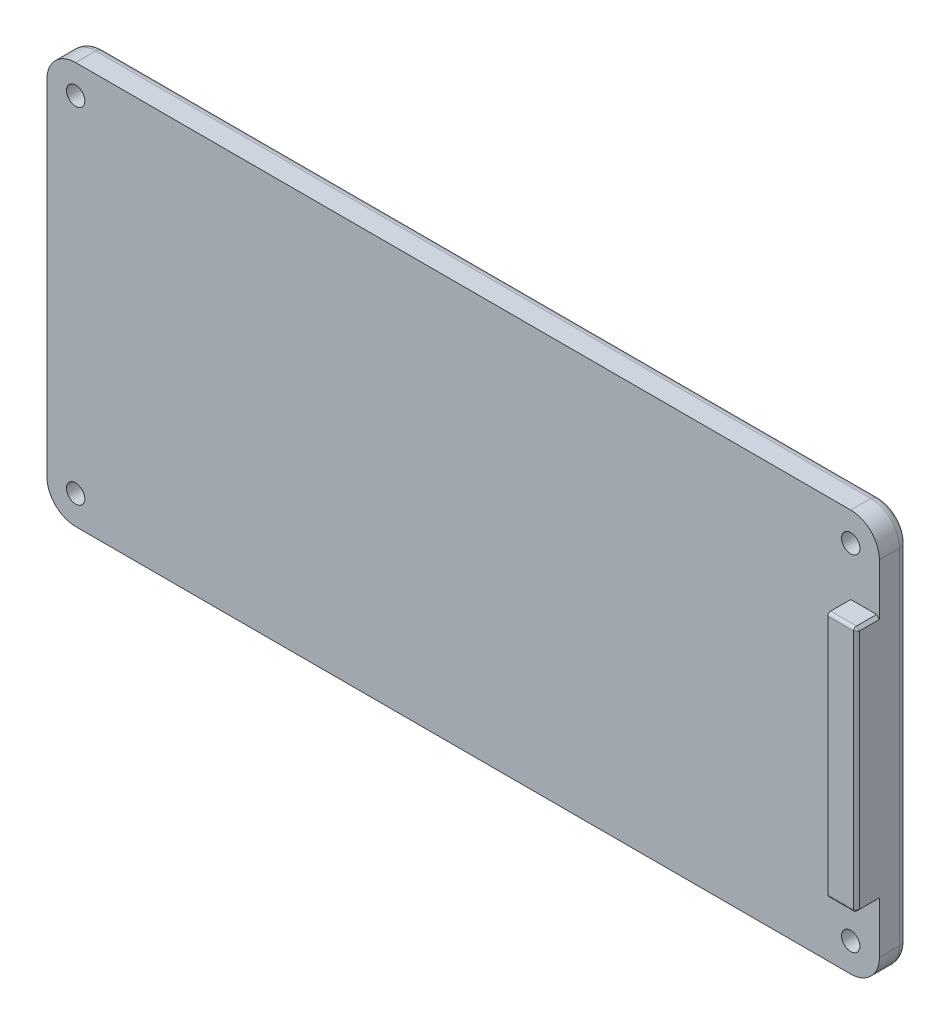
SolidWorks part; units mm, degrees
ref_plane "Ebene vorne" through (0, 0, 0) normal (0, 0, 1) x (1, 0, 0)
ref_plane "Ebene oben" through (0, 0, 0) normal (0, 1, 0) x (1, 0, 0)
ref_plane "Ebene rechts" through (0, 0, 0) normal (1, 0, 0) x (0, 0, -1)
sketch "Skizze1" plane through (0, 0, 0) normal (0, 0, 1) x (1, 0, 0)
  line L1 (-72.5, -35) -> (72.5, -35)
  line L2 (-72.5, -35) -> (-72.5, 35)
  line L3 (-72.5, 35) -> (72.5, 35)
  line L4 (72.5, -35) -> (72.5, 35)
  line L5 (-72.5, -35) -> (72.5, 35) construction
  line L6 (-72.5, 35) -> (72.5, -35) construction
  point P0 (0, 0)
  dimension "D1" = 70
  dimension "D2" = 145
extrude "Aufsatz-Linear austragen1" add sketch "Skizze1" along normal blind 5
fillet "Verrundung1" radius 5 4 edges at (72.5, -35, 2.5) (-72.5, -35, 2.5) (72.5, 35, 2.5) (-72.5, 35, 2.5)
hole_wizard "Formsenkung für M3 Linsensenkschraube mit Schlitz1" positions "Skizze2" profile "Skizze4" countersink size "M3" standard "DIN" end condition through all
sketch "Skizze2" plane through (0, 0, 0) normal (0, 0, -1) x (-1, 0, 0)
  point P0 (-67.5, 30)
  point P3 (-67.5, -30)
  point P6 (67.5, 30)
  point P9 (67.5, -30)
sketch "Skizze4" plane through (67.5, 30, 0) normal (1, 0, 0) x (0, 1, 0)
  line L0 (0, 0) -> (0, 5)
  line L1 (0, 5) -> (1.6, 5)
  line L2 (1.6, 5) -> (1.6, 2.55)
  line L3 (1.6, 2.55) -> (3.15, 1)
  line L4 (3.15, 1) -> (3.15, 0)
  line L6 (3.15, 0) -> (0, 0)
  line L7 (-1.6, 2.55) -> (-3.15, 1) construction
  line L11 (0, -6.35) -> (0, 107.95) construction
  dimension "Bohrerdurchmesser" = 3.2
  dimension "Bohrungstiefe" = 5
  dimension "Senkdurchmesser" = 6.3
  dimension "Senkwinkel" = 90
  dimension "Kopfspielraum" = 1
sketch "Skizze5" plane through (0, 0, 5) normal (0, 0, 1) x (1, 0, 0)
  line L5 (72.5, -30) -> (72.5, 30) construction
  line L6 (72.5, 21.5) -> (67.5, 21.5)
  line L7 (72.5, 21.5) -> (72.5, -21.5)
  line L8 (72.5, -21.5) -> (67.5, -21.5)
  line L9 (67.5, 21.5) -> (67.5, -21.5)
  point P6 (72.5, -38.2404)
  point P7 (72.5, 0)
  point P8 (72.5, 0)
  dimension "D1" = 43
  dimension "D2" = 5
extrude "Aufsatz-Linear austragen2" add sketch "Skizze5" along normal blind 4
fillet "Verrundung2" radius 0.5 2 edges at (70, -21.5, 9) (70, 21.5, 9)
chamfer "Fase1" distance 0.5 angle 45 5 edges at (72.5, -21.5, 6.75) (72.5, 21.5, 6.75) (72.5, 0, 9) (72.5, -21.3536, 8.8536) (72.5, 21.3536, 8.8536)
fillet "Verrundung3" radius 1.5 8 edges at (71.0355, -33.5355, 0) (0, -35, 0) (-71.0355, -33.5355, 0) (-72.5, 0, 0) (-71.0355, 33.5355, 0) (0, 35, 0) (71.0355, 33.5355, 0) (72.5, 0, 0)
